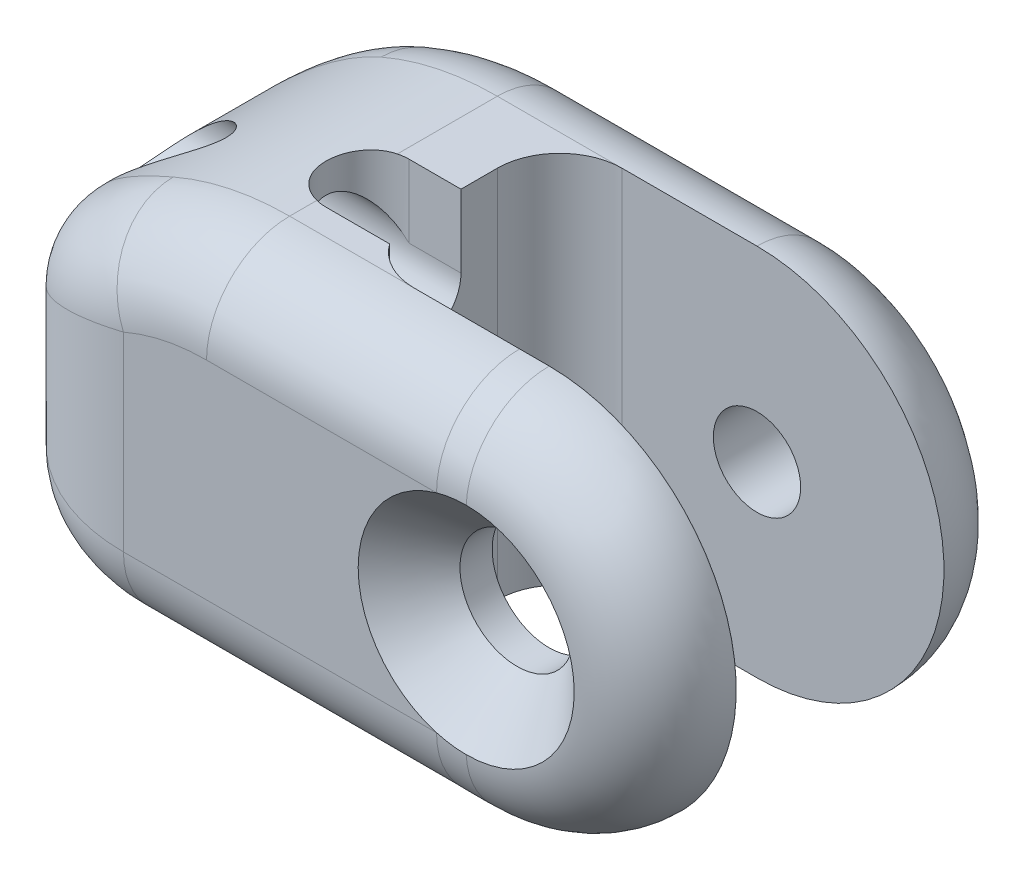
SolidWorks part; units mm, degrees
ref_plane "Front Plane" through (0, 0, 0) normal (0, 0, 1) x (1, 0, 0)
ref_plane "Top Plane" through (0, 0, 0) normal (0, 1, 0) x (1, 0, 0)
ref_plane "Right Plane" through (0, 0, 0) normal (1, 0, 0) x (0, 0, -1)
sketch "Sketch2" plane through (0, 0, 0) normal (0, 1, 0) x (1, 0, 0)
  line L0 (-2, 9) -> (23.5, 9)
  line L1 (23.5, 9) -> (23.5, 5)
  line L2 (23.5, 5) -> (8, 5)
  line L3 (5, 2) -> (5, -2)
  line L4 (8, -5) -> (23.5, -5)
  line L5 (23.5, -5) -> (23.5, -9)
  line L8 (-49.3622, 0) -> (56.3776, 0) construction
  line L9 (0, 21.2372) -> (0, -19.0689) construction
  line L10 (5, 2) -> (8, 2) construction
  line L11 (8, 2) -> (8, 5) construction
  line L16 (-2, -9) -> (23.5, -9)
  arc A0 (8, 5) -> (5, 2) centre (8, 2) ccw
  arc A1 (8, -5) -> (5, -2) centre (8, -2) cw
  arc A3 (-2, 9) -> (-2, -9) centre (-2, 0) ccw
  point P13 (8, 2)
  dimension "D2" = 18
  dimension "D3" = 4
  dimension "D4" = 18.5
  dimension "D5" = 10
  dimension "D6" = 3
  dimension "D7" = 3
  dimension "D8" = 5
  dimension "D9" = 25.5
extrude "Boss-Extrude1" add sketch "Sketch2" along normal blind 18
sketch "Sketch5" plane through (0, 0, 9) normal (0, 0, 1) x (1, 0, 0)
  line L0 (-13.5058, 9) -> (31.8434, 9) construction
  line L1 (-2, 18) -> (-2, 0) construction
  line L2 (23.5, 18) -> (23.5, 0) construction
  line L3 (-2, 18) -> (23.5, 18) construction
  line L4 (14.5, 18) -> (14.5, 0) construction
  line L5 (-11, 0) -> (-2, 0) construction
  line L7 (-12, 0) -> (-12, 4)
  line L8 (-12, 0) -> (14.5, 0)
  line L9 (2, 18) -> (14.5, 18)
  arc A1 (14.5, 0) -> (14.5, 18) centre (14.5, 9) ccw
  arc A2 (2, 18) -> (-12, 4) centre (2, 4) ccw
  dimension "D2" = 4
  dimension "D1" = 9
  dimension "D3" = 10
extrude "Cut-Extrude1" cut sketch "Sketch5" against normal blind 20 flip side to cut
sketch "Sketch6" plane through (0, 0, 9) normal (0, 0, 1) x (1, 0, 0)
  line L0 (14.5, 0) -> (14.5, 18) construction
  point P4 (14.5, 9)
hole_wizard "CSK for M5 Countersunk Flat Head Screw1" positions "Sketch7" profile "Sketch8" countersink size "M5" standard "DIN" end condition up to next
sketch "Sketch7" plane through (0, 0, 9) normal (0, 0, 1) x (1, 0, 0)
  point P0 (14.5, 9)
sketch "Sketch8" plane through (14.5, 9, 9) normal (1, 0, 0) x (0, -1, 0)
  line L0 (0, 0) -> (0, 4)
  line L1 (0, 4) -> (2.75, 4)
  line L2 (2.75, 4) -> (2.75, 2.45)
  line L3 (2.75, 2.45) -> (5.2, 0)
  line L5 (5.2, 0) -> (0, 0)
  line L6 (-2.75, 2.45) -> (-5.2, 0) construction
  line L11 (0, -6.35) -> (0, 107.95) construction
  dimension "Thru Hole Dia." = 5.5
  dimension "Thru Hole Depth" = 4
  dimension "Near C'Sink Dia." = 10.4
  dimension "Near C'Sink Angle" = 90
hole_wizard "M5 Tapped Hole1" positions "Sketch9" profile "Sketch11" tap size "M5" standard "DIN" end condition through all
sketch "Sketch9" plane through (0, 0, 9) normal (0, 0, 1) x (1, 0, 0)
  point P0 (14.5, 9)
sketch "Sketch11" plane through (14.5, 9, 9) normal (1, 0, 0) x (0, -1, 0)
  line L0 (0, 0) -> (0, 18)
  line L1 (0, 18) -> (2.1, 18)
  line L2 (2.1, 18) -> (2.1, 3.1)
  line L3 (2.1, 3.1) -> (5.2, 0)
  line L5 (5.2, 0) -> (0, 0)
  line L6 (-2.1, 3.1) -> (-5.2, 0) construction
  line L11 (0, -6.35) -> (0, 107.95) construction
  dimension "Thru Tap Drill Dia." = 4.2
  dimension "Thru Tap Drill Depth" = 18
  dimension "Near C'Sink Dia." = 10.4
  dimension "Near C'Sink Angle" = 90
cosmetic thread "Hole Thread1" parameters "D2"=5
fillet "Fillet2" radius 4 9 edges at (-10.9995, 9.1973, -0.0903) (-0.0212, 17.8533, -9) (8.25, 18, -9) (23.5, 9, -9) (-0.0212, 17.8533, 9) (8.25, 18, 9) (6.25, 0, 9) (-11, 0, 0) (6.25, 0, -9)
sketch "Sketch13" plane through (5, 0, 0) normal (1, 0, 0) x (0, 0, -1)
  line L0 (-1.75, -2.2721) -> (-1.75, 20.0856) construction
  line L1 (-2, 0) -> (2, 0) construction
  line L2 (-2, 18) -> (2, 18) construction
  circle A0 centre (-1.75, 14.5) radius 2
  point P4 (0, 0)
  dimension "D2" = 3.5
  dimension "D3" = 4
  dimension "D1" = 1.75
extrude "Cut-Extrude2" cut sketch "Sketch13" against normal through all both and the other way through all
sketch "Sketch14" plane through (0, 18, 0) normal (0, 1, 0) x (1, 0, 0)
  line L0 (5, 0) -> (-14.1432, 0) construction
  line L3 (5, -2) -> (5, 2) construction
  line L4 (2.5, -3.75) -> (7.4532, -3.75)
  line L5 (2.5, 0.25) -> (7.4532, 0.25)
  line L6 (7.4532, 0.25) -> (7.4532, -3.75)
  arc A0 (2.5, 0.25) -> (2.5, -3.75) centre (2.5, -1.75) ccw
  dimension "D1" = 1.75
  dimension "D2" = 2.5
extrude "Cut-Extrude3" cut sketch "Sketch14" against normal blind 3.5
